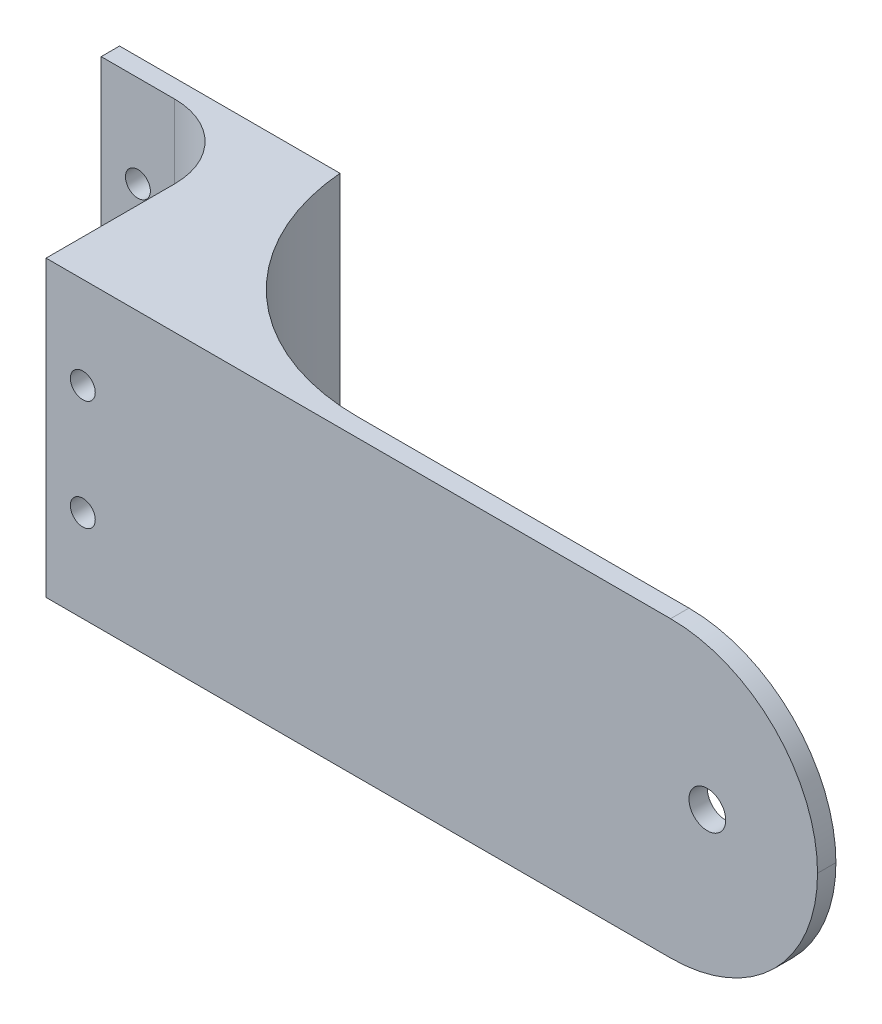
SolidWorks part; units mm, degrees
material "6061-T6 (SS)"
ref_plane "Front Plane" through (0, 0, 0) normal (0, 0, 1) x (1, 0, 0)
ref_plane "Top Plane" through (0, 0, 0) normal (0, 1, 0) x (1, 0, 0)
ref_plane "Right Plane" through (0, 0, 0) normal (1, 0, 0) x (0, 0, -1)
ref_plane "Plane1" through (0, 0, 15.875) normal (0, 0, 1) x (1, 0, 0)
sketch "Sketch1" plane through (0, 0, 15.875) normal (0, 0, 1) x (1, 0, 0)
  line L0 (0, -25.4) -> (0, 25.4) construction
  line L1 (0, 25.4) -> (-38.1, 25.4) construction
  line L2 (-38.1, 25.4) -> (-38.1, -25.4)
  line L3 (-38.1, -25.4) -> (-25.4, -25.4)
  line L5 (0, 25.4) -> (-38.1, 25.4)
  line L6 (-25.4, -25.4) -> (0, -25.4)
  line L7 (0, -25.4) -> (0, 25.4)
  point P2 (0, 0)
  dimension "D1" = 50.8
  dimension "D2" = 38.1
  dimension "D3" = 12.7
extrude "Boss-Extrude1" add sketch "Sketch1" along normal blind 3.175
ref_plane "Plane2" through (0, 0, 50.8) normal (0, 0, 1) x (1, 0, 0)
sketch "Sketch2" plane through (0, 0, 50.8) normal (0, 0, 1) x (1, 0, 0)
  line L0 (0, -25.4) -> (0, 25.4) construction
  line L1 (0, 25.4) -> (-12.7, 25.4)
  line L2 (-12.7, 25.4) -> (-12.7, -25.4)
  line L3 (-12.7, -25.4) -> (0, -25.4)
  line L4 (0, -25.4) -> (0, 25.4)
  point P2 (0, 0)
  dimension "D1" = 50.8
  dimension "D2" = 12.7
extrude "Boss-Extrude2" add sketch "Sketch2" against normal up to surface (31.75 mm away) up to face at (-19.05, 0, 19.05)
fillet "Fillet1" radius 12.7 1 edges at (-12.7, 0, 19.05)
sketch "Sketch3" plane through (0, 0, 50.8) normal (0, 0, 1) x (1, 0, 0)
  line L0 (0, 0) -> (0, 25.4) construction
  line L1 (0, -25.4) -> (0, 25.4) construction
  line L2 (0, 25.4) -> (101.6, 25.4)
  line L3 (101.6, 25.4) -> (120.65, 25.4)
  line L4 (120.65, 25.4) -> (120.65, -25.4)
  line L5 (120.65, -25.4) -> (0, -25.4)
  line L6 (0, -25.4) -> (-12.7, -25.4)
  line L7 (-12.7, -25.4) -> (-12.7, 25.4)
  line L8 (-12.7, 25.4) -> (0, 25.4)
  dimension "D1" = 19.05
  dimension "D2" = 101.6
  dimension "D3" = 50.8
  dimension "D4" = 12.7
extrude "Boss-Extrude3" add sketch "Sketch3" along normal blind 3.175
fillet "Fillet2" radius 38.1 1 edges at (0, 0, 50.8)
sketch "Sketch4" plane through (0, 0, 53.975) normal (0, 0, 1) x (1, 0, 0)
  line L0 (0, 0) -> (-55.8335, 0) construction
  line L1 (0, -25.4) -> (0, 25.4) construction
  line L2 (-38.1, 25.4) -> (-38.1, -25.4) construction
  line L3 (-38.1, 25.4) -> (-38.1, -25.4) construction
  line L7 (0, -25.4) -> (0, 25.4) construction
  line L8 (0, -25.4) -> (0, 25.4) construction
  circle A0 centre (-6.35, 9.525) radius 2.1527
  circle A2 centre (-31.75, 9.525) radius 2.1527
  circle A4 centre (-6.35, -9.525) radius 2.1527
  circle A5 centre (-31.75, -9.525) radius 2.1527
  dimension "D1" = 4.3053
  dimension "D2" = 6.35
  dimension "D3" = 9.525
  dimension "D4" = 19.05
  dimension "D5" = 25.4
  dimension "D6" = 38.1
extrude "Cut-Extrude1" cut sketch "Sketch4" against normal up to surface (38.1 mm away) up to face at (-19.05, 0, 15.875)
fillet "Fillet3" radius 25.4 2 edges at (120.65, -25.4, 52.3875) (120.65, 25.4, 52.3875)
sketch "Sketch5" plane through (0, 0, 53.975) normal (0, 0, 1) x (1, 0, 0)
  line L0 (0, -25.4) -> (0, 25.4) construction
  line L1 (0, -25.4) -> (0, 25.4) construction
  line L2 (95.25, 25.4) -> (-12.7, 25.4) construction
  line L3 (82.5851, -19.0149) -> (120.6149, 19.0149) construction
  line L4 (118.089, -16.489) -> (85.111, 16.489) construction
  line L5 (101.6, 0) -> (101.6, -34.636) construction
  circle A0 centre (101.6, 0) radius 3.175 construction
  circle A1 centre (101.6, 0) radius 9.525
  circle A2 centre (101.6, 0) radius 13 construction
  circle A4 centre (110.7924, 9.1924) radius 1.5875
  circle A5 centre (110.7924, -9.1924) radius 1.5875
  circle A6 centre (92.4076, -9.1924) radius 1.5875
  circle A7 centre (92.4076, 9.1924) radius 1.5875
  point P21 (101.6, 0)
  point P24 (101.6, 0)
  dimension "D2" = 6.35
  dimension "D3" = 19.05
  dimension "D4" = 26
  dimension "D5" = 3.175
  dimension "D6" = 25.4
  dimension "D7" = 45
  dimension "D8" = 90
extrude "Cut-Extrude2" [suppressed] cut sketch "Sketch5" against normal up to surface (3.175 mm away)
sketch "Sketch6" [suppressed] plane through (0, 0, 53.975) normal (0, 0, 1) x (1, 0, 0)
  line L0 (80.4908, -21.1092) -> (122.7092, 21.1092) construction
  line L1 (119.8449, -18.2449) -> (83.3551, 18.2449) construction
  line L2 (101.6, 0) -> (101.6, -31.1994) construction
  line L3 (95.25, 25.4) -> (-12.7, 25.4) construction
  circle A0 centre (101.6, 0) radius 8.55
  circle A1 centre (101.6, 0) radius 11 construction
  circle A2 centre (93.8218, 7.7782) radius 1.5875
  circle A3 centre (109.3782, 7.7782) radius 1.5875
  circle A4 centre (109.3782, -7.7782) radius 1.5875
  circle A5 centre (93.8218, -7.7782) radius 1.5875
  circle A6 centre (93.8218, 7.7782) radius 2.75 construction
  point P2 (0, 0)
  point P8 (101.6, 0)
  point P10 (101.6, 0)
  point P23 (95.7664, 5.8336)
  point P24 (95.5542, 6.0458)
  dimension "D2" = 17.1
  dimension "D3" = 22
  dimension "D6" = 3.175
  dimension "D8" = 5.5
  dimension "D1" = 101.6
  dimension "D4" = 45
  dimension "D5" = 45
  dimension "D7" = 25.4
extrude "Cut-Extrude3" [suppressed] cut sketch "Sketch6" against normal up to surface (3.175 mm away)
sketch "Sketch7" plane through (0, 0, 53.975) normal (0, 0, 1) x (1, 0, 0)
  line L0 (95.25, 25.4) -> (-12.7, 25.4) construction
  circle A0 centre (101.6, 0) radius 3.175
  point P2 (0, 0)
  dimension "D2" = 6.35
  dimension "D1" = 101.6
  dimension "D3" = 25.4
extrude "Cut-Extrude4" cut sketch "Sketch7" against normal up to next
